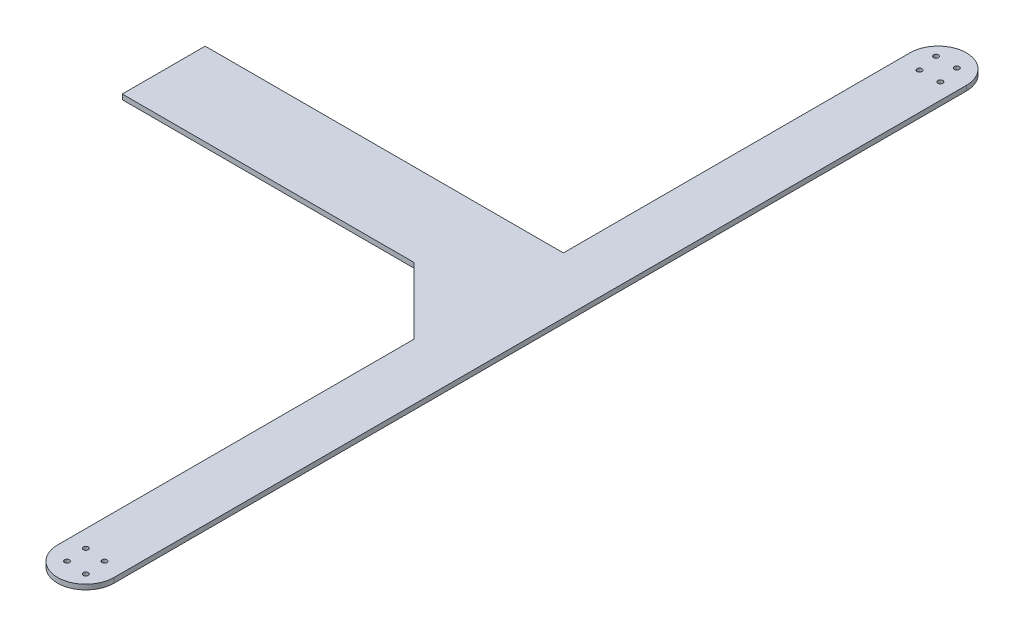
SolidWorks part; units mm, degrees
ref_plane "Front Plane" through (0, 0, 0) normal (0, 0, 1) x (1, 0, 0)
ref_plane "Top Plane" through (0, 0, 0) normal (0, 1, 0) x (1, 0, 0)
ref_plane "Right Plane" through (0, 0, 0) normal (1, 0, 0) x (0, 0, -1)
sketch "Sketch1" plane through (0, 0, 0) normal (0, 1, 0) x (1, 0, 0)
  line L0 (0, 0) -> (176, 0)
  line L1 (216, -40) -> (216, -255)
  line L2 (0, 0) -> (0, 50)
  line L3 (0, 50) -> (216, 50)
  line L4 (216, 50) -> (216, 259.0603)
  line L5 (250, -255) -> (250, 259.0603)
  line L6 (50, -120) -> (250, -120) construction
  line L7 (50, 150) -> (50, -120) construction
  line L8 (50, 150) -> (250, 120) construction
  line L9 (176, 0) -> (216, -40)
  line L10 (227.9078, 252.8902) -> (238.0922, 265.2304) construction
  line L11 (240.327, 253.0134) -> (225.673, 265.1073) construction
  line L12 (227.3431, -260.6569) -> (238.6569, -249.3431) construction
  line L14 (226.2825, -248.2825) -> (239.7175, -261.7175) construction
  arc A0 (216, -255) -> (250, -255) centre (233, -255) ccw
  arc A1 (216, 259.0603) -> (250, 259.0603) centre (233, 259.0603) cw
  circle A2 centre (233, -255) radius 135 construction
  circle A3 centre (233, 259.0603) radius 135 construction
  circle A4 centre (238.0922, 265.2304) radius 1.5
  circle A5 centre (225.673, 265.1073) radius 1.5
  circle A6 centre (227.9078, 252.8902) radius 1.5
  circle A7 centre (240.327, 253.0134) radius 1.5
  circle A8 centre (226.2825, -248.2825) radius 1.5
  circle A9 centre (238.6569, -249.3431) radius 1.5
  circle A10 centre (239.7175, -261.7175) radius 1.5
  circle A11 centre (227.3431, -260.6569) radius 1.5
  point P1 (216, 0)
  point P12 (250, 120)
  point P13 (250, -120)
  point P14 (50, 150)
  point P15 (50, -120)
  dimension "D1" = 17
  dimension "D3" = 270
  dimension "D4" = 270
  dimension "D12" = 3
  dimension "D13" = 3
  dimension "D14" = 3
  dimension "D15" = 3
  dimension "D20" = 3
  dimension "D21" = 3
  dimension "D22" = 3
  dimension "D23" = 3
  dimension "D2" = 50
  dimension "D5" = 240
  dimension "D6" = 200
  dimension "D7" = 50
  dimension "D8" = 120
  dimension "D9" = 16
  dimension "D10" = 19
  dimension "D16" = 270
  dimension "D17" = 45
  dimension "D18" = 16
  dimension "D19" = 19
extrude "Boss-Extrude1" add sketch "Sketch1" along normal blind 3 contours L1 A0 L5 L8 L4 L3 L7 L0 L9 A11 A10 A9 A8 | L7 L3 L2 L0 | A1 L4 L8 L5 A7 A6 A5 A4 region at (187.0831, 0, -9.9081)
